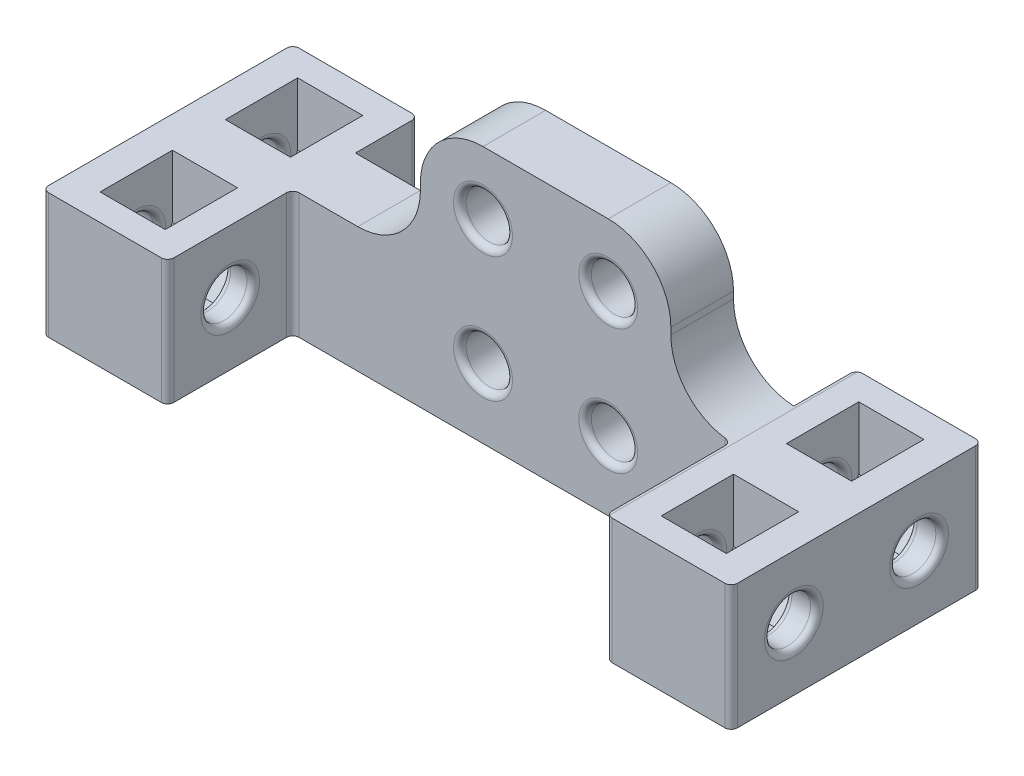
SolidWorks part; units mm, degrees
ref_plane "Front Plane" through (0, 0, 0) normal (0, 0, 1) x (1, 0, 0)
ref_plane "Top Plane" through (0, 0, 0) normal (0, 1, 0) x (1, 0, 0)
ref_plane "Right Plane" through (0, 0, 0) normal (1, 0, 0) x (0, 0, -1)
sketch "Sketch1" plane through (0, 0, 0) normal (0, 0, 1) x (1, 0, 0)
  line L0 (-34.925, -13.0426) -> (34.925, -13.0426)
  line L1 (-34.925, -13.0426) -> (-34.925, -0.3426)
  line L2 (-34.925, -0.3426) -> (-9.29, -0.3426)
  line L3 (34.925, -13.0426) -> (34.925, -0.3426)
  line L4 (-9.29, -0.3426) -> (-9.29, 13.0426)
  line L5 (-9.29, 13.0426) -> (16.11, 13.0426)
  line L6 (16.11, 13.0426) -> (16.11, -0.3426)
  line L7 (16.11, -0.3426) -> (34.925, -0.3426)
  circle A0 centre (-2.94, 6.6926) radius 2.3495
  circle A1 centre (9.76, 6.6926) radius 2.3495
  circle A2 centre (9.76, -6.0074) radius 2.3495
  circle A3 centre (-2.94, -6.0074) radius 2.3495
  dimension "D1" = 4.699
  dimension "D2" = 9.76
  dimension "D3" = 16.11
  dimension "D4" = 34.925
  dimension "D5" = 2.94
  dimension "D6" = 9.29
  dimension "D7" = 34.925
  dimension "D8" = 6.6926
  dimension "D9" = 13.0426
  dimension "D10" = 0.3426
  dimension "D11" = 6.0074
  dimension "D13" = 13.0426
extrude "Boss-Extrude1" add sketch "Sketch1" along normal mid plane 6.35
sketch "Sketch2" plane through (0, 0, -3.175) normal (0, 0, -1) x (-1, 0, 0)
  line L0 (34.925, -0.3426) -> (22.225, -0.3426)
  line L1 (9.29, -0.3426) -> (34.925, -0.3426) construction
  line L2 (22.225, -0.3426) -> (22.225, -13.0426)
  line L3 (34.925, -13.0426) -> (-34.925, -13.0426) construction
  line L4 (22.225, -13.0426) -> (34.925, -13.0426)
  line L5 (34.925, -0.3426) -> (34.925, -13.0426) construction
  line L6 (34.925, -13.0426) -> (34.925, -0.3426)
  line L7 (-34.925, -0.3426) -> (-22.225, -0.3426)
  line L8 (-34.925, -0.3426) -> (-16.11, -0.3426) construction
  line L9 (-22.225, -0.3426) -> (-22.225, -13.0426)
  line L10 (-22.225, -13.0426) -> (-34.925, -13.0426)
  line L11 (-34.925, -13.0426) -> (-34.925, -0.3426) construction
  line L12 (-34.925, -13.0426) -> (-34.925, -0.3426)
  dimension "D1" = 12.7
  dimension "D2" = 12.7
extrude "Boss-Extrude2" add sketch "Sketch2" along normal mid plane 25.4
sketch "Sketch4" plane through (-34.925, 0, 0) normal (-1, 0, 0) x (0, 0, 1)
  line L0 (-15.875, -13.0426) -> (-15.875, -0.3426) construction
  line L1 (9.525, -13.0426) -> (-15.875, -13.0426) construction
  circle A0 centre (-9.525, -6.6926) radius 2.3368
  circle A1 centre (3.175, -6.6926) radius 2.3368
  dimension "D3" = 4.6736
  dimension "D1" = 6.35
  dimension "D2" = 12.7
  dimension "D4" = 6.35
extrude "Cut-Extrude1" cut sketch "Sketch4" against normal blind 19.05
extrude "Cut-Extrude2" cut sketch "Sketch4<2>" along normal blind 19.05 from surface starting at face at (34.925, -6.6926, -3.175)
sketch "Sketch4<2>" plane through (-34.925, 0, 0) normal (-1, 0, 0) x (0, 0, 1) same geometry as "Sketch4"
sketch "Sketch5" plane through (-34.925, 0, 0) normal (-1, 0, 0) x (0, 0, 1)
  line L0 (-13.1912, -6.6926) -> (-13.1912, 2.6021)
  line L1 (-7.6919, -3.5176) -> (-11.3581, -3.5176) construction
  line L2 (-11.3581, -3.5176) -> (-13.1912, -6.6926) construction
  line L3 (-13.1912, -6.6926) -> (-11.3581, -9.8676)
  line L4 (-11.3581, -9.8676) -> (-7.6919, -9.8676)
  line L5 (-7.6919, -9.8676) -> (-5.8588, -6.6926)
  line L6 (-5.8588, -6.6926) -> (-7.6919, -3.5176) construction
  line L7 (5.0081, -3.5176) -> (1.3419, -3.5176) construction
  line L8 (1.3419, -3.5176) -> (-0.4912, -6.6926) construction
  line L9 (-0.4912, -6.6926) -> (1.3419, -9.8676)
  line L10 (1.3419, -9.8676) -> (5.0081, -9.8676)
  line L11 (5.0081, -9.8676) -> (6.8412, -6.6926)
  line L12 (6.8412, -6.6926) -> (5.0081, -3.5176) construction
  line L13 (-13.1912, 2.6021) -> (-5.8588, 2.6021)
  line L14 (-5.8588, 2.6021) -> (-5.8588, -6.6926)
  line L15 (-0.4912, -6.6926) -> (-0.4912, 3.296)
  line L16 (-0.4912, 3.296) -> (6.8412, 3.296)
  line L17 (6.8412, 3.296) -> (6.8412, -6.6926)
  circle A0 centre (-9.525, -6.6926) radius 3.175 construction
  circle A1 centre (3.175, -6.6926) radius 3.175 construction
  dimension "D1" = 6.35
extrude "Cut-Extrude3" cut sketch "Sketch5" against normal blind 6.604 from offset 3.175 offset against normal yes
mirror "Mirror1" about plane through (0, 0, 0) normal (1, 0, 0) of "Cut-Extrude3"
fillet "Fillet1" radius 0.635 32 edges at (-15.875, -6.6926, 3.175) (15.875, -6.6926, 3.175) (-0.5905, -6.0074, -3.175) (-0.5905, -6.0074, 3.175) (12.1095, -6.0074, -3.175) (12.1095, -6.0074, 3.175) (12.1095, 6.6926, -3.175) (12.1095, 6.6926, 3.175) (-0.5905, 6.6926, -3.175) (-0.5905, 6.6926, 3.175) (-31.75, -6.6926, 0.8382) (-34.925, -6.6926, 5.5118) (-34.925, -6.6926, -7.1882) (-31.75, -6.6926, -7.1882) (-25.146, -6.6926, -7.1882) (-22.225, -9.0294, -9.525) (25.146, -6.6926, -11.8618) (22.225, -4.3558, -9.525) (34.925, -6.6926, -7.1882) (31.75, -6.6926, -11.8618) (31.75, -6.6926, 5.5118) (34.925, -6.6926, 5.5118) (-15.875, -6.6926, 0.8382) (-19.05, -9.0294, 3.175) (-22.225, -6.6926, 5.5118) (-19.05, -4.3558, 3.175) (-25.146, -6.6926, 0.8382) (19.05, -9.0294, 3.175) (15.875, -6.6926, 0.8382) (19.05, -4.3558, 3.175) (22.225, -6.6926, 5.5118) (25.146, -6.6926, 5.5118)
fillet "Fillet2" radius 6.35 4 edges at (-9.29, 13.0426, 0) (16.11, 13.0426, 0) (16.11, -0.3426, 0) (-9.29, -0.3426, 0)
fillet "Fillet3" radius 0.635 10 edges at (34.925, -6.6926, -15.875) (22.225, -6.6904, -15.875) (22.225, -6.6904, -3.175) (-22.225, -6.6926, -3.175) (-22.225, -6.6926, -15.875) (-34.925, -6.6926, 9.525) (-22.225, -6.6926, 9.525) (22.225, -6.6904, 9.525) (34.925, -6.6926, 9.525) (-34.925, -6.6926, -15.875)
ref_plane "Plane1" through (0, 0, -15.875) normal (0, 0, -1) x (-1, 0, 0)
mirror "Mirror2" about plane through (0, 0, -15.875) normal (0, 0, -1) of bodies 106
delete or keep bodies "Body-Delete/Keep 1" type delete bodies bodies 106
